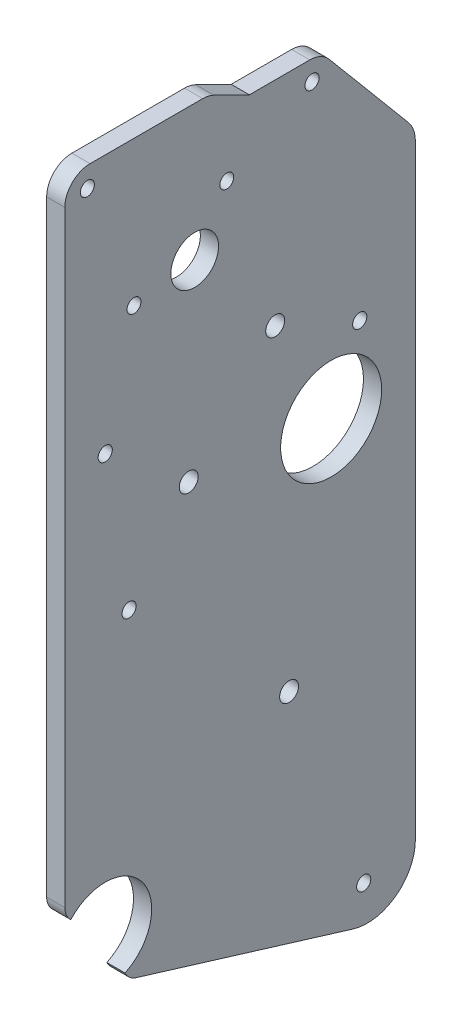
SolidWorks part; units mm, degrees
material "Acrylic (Medium-high impact)"
ref_plane "Front" through (0, 0, 0) normal (0, 0, 1) x (1, 0, 0)
ref_plane "Top" through (0, 0, 0) normal (0, 1, 0) x (1, 0, 0)
ref_plane "Right" through (0, 0, 0) normal (1, 0, 0) x (0, 0, -1)
ref_axis "side-side" through (80.9, 0, 0) along (-1, 0, 0)
ref_axis "up-down" through (0, 50, 0) along (0, -1, 0)
ref_axis "front-back" through (0, 0, -80.9) along (0, 0, 1)
sketch "Sketch1" plane through (0, 0, 0) normal (1, 0, 0) x (0, 0, -1)
  line L3 (-284.7019, 193.761) -> (-287.8294, 193.2851)
  line L5 (-286.7762, 186.3647) -> (-283.6486, 186.8407)
  line L32 (-189.5806, 171.954) -> (-230.0702, 220.2077)
  line L33 (-115.8892, 171.954) -> (-189.5806, 171.954)
  line L34 (-105.8892, 88.0777) -> (-105.8892, 161.954)
  line L35 (-120.7593, 66.032) -> (-105.8892, 88.0777)
  line L36 (-120.7593, 36.576) -> (-120.7593, 66.032)
  line L37 (-184.0537, -1.524) -> (-158.1882, -1.524)
  line L38 (-179.5414, 5.1658) -> (-184.0537, -1.524)
  line L39 (-183.2787, 7.6866) -> (-179.5414, 5.1658)
  line L40 (-189.4913, -1.524) -> (-183.2787, 7.6866)
  line L41 (-202.3597, -1.524) -> (-189.4913, -1.524)
  line L42 (-238.7597, 32.254) -> (-202.3597, -1.524)
  line L43 (-289.341, 47.7141) -> (-238.7597, 32.254)
  line L44 (-296.5313, 221.1604) -> (-296.5313, 57.4304)
  line L45 (-261.8637, 227.5104) -> (-290.1813, 227.5104)
  line L46 (-250.1193, 222.476) -> (-259.0691, 226.8624)
  line L47 (-234.9346, 222.476) -> (-250.1193, 222.476)
  circle A2 centre (-229.5573, 141.6606) radius 2.3813
  circle A4 centre (-286.3713, 57.4304) radius 2.3813
  circle A6 centre (-112.7323, 86.2169) radius 1.85
  circle A8 centre (-191.956, 48) radius 1.85
  circle A10 centre (-199.956, 40) radius 1.85
  circle A12 centre (-199.956, 168) radius 1.85
  circle A14 centre (-199.956, 152) radius 1.85
  circle A16 centre (-199.956, 72) radius 1.85
  circle A18 centre (-280.3713, 125.4304) radius 1.8415
  circle A20 centre (-199.956, 56) radius 1.85
  circle A22 centre (-240.1331, 87.5182) radius 2.3813
  circle A24 centre (-221.3713, 36.4304) radius 1.778
  circle A26 centre (-265.3667, 145.7893) radius 2.3813
  circle A28 centre (-286.3713, 162.4304) radius 1.8415
  arc A36 (-105.8892, 161.954) -> (-115.8892, 171.954) centre (-115.8892, 161.954) ccw
  arc A37 (-120.7593, 36.576) -> (-158.1882, -1.524) centre (-120.0821, -1.524) ccw
  arc A38 (-296.5313, 57.4304) -> (-289.341, 47.7141) centre (-286.3713, 57.4304) ccw
  arc A39 (-290.1813, 227.5104) -> (-296.5313, 221.1604) centre (-290.1813, 221.1604) ccw
  arc A40 (-259.0691, 226.8624) -> (-261.8637, 227.5104) centre (-261.8637, 221.1604) ccw
  arc A41 (-230.0702, 220.2077) -> (-234.9346, 222.476) centre (-234.9346, 216.126) ccw
  circle A42 centre (-222.3713, 159.4304) radius 1.8415
  circle A44 centre (-290.8713, 222.4304) radius 1.8415
  circle A46 centre (-234.3713, 217.4304) radius 1.8415
  arc A62 (-287.8294, 193.2851) -> (-286.7762, 186.3647) centre (-287.3028, 189.8249) ccw
  arc A63 (-278.545, 184.4599) -> (-283.6486, 186.8407) centre (-282.8843, 181.8186) ccw
  arc A64 (-278.545, 184.4599) -> (-250.9607, 204.7189) centre (-263.8726, 193.3908) ccw
  arc A65 (-252.4172, 207.4476) -> (-250.9607, 204.7189) centre (-245.8586, 209.1952) ccw
  arc A66 (-252.4172, 207.4476) -> (-256.5272, 209.9699) centre (-255.7992, 206.5464) ccw
  arc A67 (-259.6197, 210.0327) -> (-256.5272, 209.9699) centre (-257.9391, 216.6088) ccw
  arc A68 (-259.6197, 210.0327) -> (-280.5376, 197.5524) centre (-263.8726, 193.3908) ccw
  arc A69 (-284.7019, 193.761) -> (-280.5376, 197.5524) centre (-285.4662, 198.7832) ccw
sketch "Sketch2" plane through (0, 0, 0) normal (1, 0, 0) x (0, 0, -1)
  line L2 (-247.956, 231.9223) -> (-247.956, 224)
  line L3 (-218.456, 224) -> (-247.956, 224)
  line L8 (-184.6269, 224) -> (-215.956, 224)
  line L9 (-215.956, 224) -> (-215.956, 190.282)
  line L10 (-215.956, 190.282) -> (-184.6269, 190.282)
  line L11 (-184.6269, 190.282) -> (-184.6269, 224)
  circle A2 centre (-263.8726, 193.3908) radius 11
  circle A4 centre (-255.7992, 206.5464) radius 1.5
  circle A6 centre (-279.1322, 191.0684) radius 1.5
  circle A8 centre (-263.8726, 193.3908) radius 6
  circle A10 centre (-265.3667, 145.7893) radius 4
  circle A12 centre (-240.1331, 87.5182) radius 4
  circle A14 centre (-290.8713, 222.4304) radius 1.778
  circle A16 centre (-234.3713, 217.4304) radius 1.778
  circle A18 centre (-286.3713, 162.4304) radius 1.778
  circle A20 centre (-222.3713, 159.4304) radius 1.778
  circle A22 centre (-221.3713, 36.4304) radius 1.778
  circle A24 centre (-280.3713, 125.4304) radius 1.778
  arc A25 (-277.1812, 223.3695) -> (-292.7489, 177.8345) centre (-263.8726, 193.3908) ccw
sketch "Sketch3" plane through (0, 0, 0) normal (1, 0, 0) x (0, 0, -1)
  arc A1 (-292.3631, 63.2234) -> (-289.7933, 49.8309) centre (-286.3713, 57.4304) ccw
  circle A3 centre (-286.3713, 57.4304) radius 10.668
  arc A5 (-227.7509, 40.7095) -> (-233.7915, 135.5199) centre (-240.1331, 87.5182) ccw
  circle A7 centre (-229.5573, 141.6606) radius 10.668
  circle A9 centre (-243.6293, 168.9312) radius 2.3813
  point P3 (-289.7933, 49.8309)
  point P10 (-204.2291, 120.0032)
  point P12 (-227.4589, 39.6054)
  point P14 (-233.7915, 135.5199)
sketch "Sketch4" plane through (0, 0, 0) normal (1, 0, 0) x (0, 0, -1)
  line L0 (-296.5313, 221.1604) -> (-296.5313, 57.4304) construction
  line L1 (-261.8637, 227.5104) -> (-290.1813, 227.5104) construction
  line L2 (-289.341, 47.7141) -> (-238.7597, 32.254) construction
  line L3 (-250.1193, 222.476) -> (-259.0691, 226.8624) construction
  line L4 (-278.598, 44.4305) -> (-224.0243, 27.7502)
  line L5 (-250.1193, 222.476) -> (-259.0691, 226.8624)
  line L6 (-296.5313, 221.1604) -> (-296.5313, 68.6639)
  line L7 (-261.8637, 227.5104) -> (-290.1813, 227.5104)
  line L8 (-208.3831, 191.5885) -> (-208.3831, 39.325)
  line L9 (-221.3713, 36.4304) -> (-224.0243, 27.7502) construction
  line L10 (-234.9346, 222.476) -> (-250.1193, 222.476) construction
  line L11 (-234.9346, 222.476) -> (-250.1193, 222.476)
  line L12 (-189.5806, 171.954) -> (-230.0702, 220.2077) construction
  line L13 (-210.1658, 196.4865) -> (-230.0702, 220.2077)
  line L14 (-286.3713, 57.4304) -> (-295.0293, 65.276) construction
  line L15 (-281.399, 46.8572) -> (-286.3713, 57.4304) construction
  arc A0 (-290.1813, 227.5104) -> (-296.5313, 221.1604) centre (-290.1813, 221.1604) ccw construction
  arc A1 (-259.0691, 226.8624) -> (-261.8637, 227.5104) centre (-261.8637, 221.1604) ccw construction
  arc A2 (-290.1813, 227.5104) -> (-296.5313, 221.1604) centre (-290.1813, 221.1604) ccw
  arc A3 (-259.0691, 226.8624) -> (-261.8637, 227.5104) centre (-261.8637, 221.1604) ccw
  arc A4 (-295.0293, 65.276) -> (-296.5313, 68.6639) centre (-291.9593, 68.6639) cw
  arc A5 (-278.598, 44.4305) -> (-281.399, 46.8572) centre (-277.2617, 48.8028) cw
  circle A6 centre (-286.3713, 57.4304) radius 11.684
  arc A7 (-281.399, 46.8572) -> (-295.0293, 65.276) centre (-286.3713, 57.4304) ccw
  circle A8 centre (-221.3713, 36.4304) radius 1.778 construction
  circle A9 centre (-229.5573, 141.6606) radius 12.7
  circle A10 centre (-229.5573, 141.6606) radius 12.7
  circle A11 centre (-221.3713, 36.4304) radius 1.778
  circle A12 centre (-243.6293, 168.9312) radius 2.3813
  circle A13 centre (-280.3713, 125.4304) radius 1.778 construction
  circle A14 centre (-280.3713, 125.4304) radius 1.778
  circle A15 centre (-286.3713, 162.4304) radius 1.778 construction
  circle A16 centre (-286.3713, 162.4304) radius 1.778
  circle A18 centre (-279.1322, 191.0684) radius 1.75
  circle A19 centre (-255.7992, 206.5464) radius 1.75
  circle A20 centre (-263.8726, 193.3908) radius 6 construction
  circle A21 centre (-263.8726, 193.3908) radius 6
  circle A22 centre (-290.8713, 222.4304) radius 1.778 construction
  circle A23 centre (-290.8713, 222.4304) radius 1.778
  circle A24 centre (-234.3713, 217.4304) radius 1.778 construction
  circle A25 centre (-234.3713, 217.4304) radius 1.778
  arc A26 (-208.3831, 39.325) -> (-224.0243, 27.7502) centre (-220.4865, 39.325) cw
  circle A27 centre (-222.3713, 159.4304) radius 1.778 construction
  circle A28 centre (-222.3713, 159.4304) radius 1.778
  arc A29 (-230.0702, 220.2077) -> (-234.9346, 222.476) centre (-234.9346, 216.126) ccw construction
  arc A30 (-230.0702, 220.2077) -> (-234.9346, 222.476) centre (-234.9346, 216.126) ccw
  arc A31 (-208.3831, 191.5885) -> (-210.1658, 196.4865) centre (-216.0031, 191.5885) ccw
  circle A32 centre (-265.3667, 145.7893) radius 2.3813 construction
  circle A33 centre (-265.3667, 145.7893) radius 2.3813
  circle A34 centre (-240.1331, 87.5182) radius 2.3813 construction
  circle A35 centre (-240.1331, 87.5182) radius 2.3813
  point P67 (-252.4735, 171.8567)
  dimension "D3" = 3.5
  dimension "D5" = 7.62
  dimension "D6" = 4.572
  dimension "D4" = 31.75
  dimension "D1" = 1.016
  dimension "D2" = 2.032
extrude "Boss-Extrude1" add sketch "Sketch4" against normal blind 4.572
